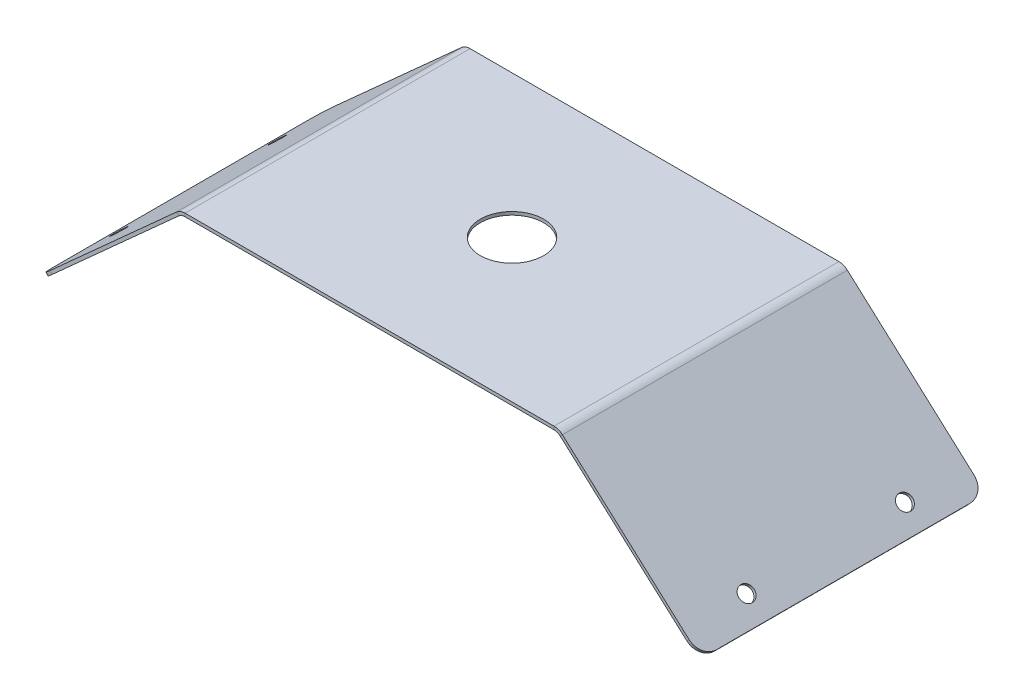
SolidWorks part; units mm, degrees
note: The reader was unsure of these and kept them because the rebuilt part matched: flange length of "Aresta-Flange1".
ref_plane "Plano frontal" through (0, 0, 0) normal (0, 0, 1) x (1, 0, 0)
ref_plane "Plano superior" through (0, 0, 0) normal (0, 1, 0) x (1, 0, 0)
ref_plane "Plano direito" through (0, 0, 0) normal (1, 0, 0) x (0, 0, -1)
sketch "Esboço1" plane through (0, 0, 0) normal (0, 1, 0) x (1, 0, 0)
  line L1 (-58.25, 45) -> (58.25, 45)
  line L2 (-58.25, 45) -> (-58.25, -45)
  line L3 (-58.25, -45) -> (58.25, -45)
  line L4 (58.25, 45) -> (58.25, -45)
  line L5 (-58.25, 45) -> (58.25, -45) construction
  line L6 (-58.25, -45) -> (58.25, 45) construction
  point P0 (0, 0)
  dimension "D1" = 116.5
  dimension "D2" = 90
base flange "Flange-base1" sketch "Esboço1" thickness 1 reverse thickness direction no parameters "D1"=3
edge flange "Aresta-Flange1" sketch "Esboço10" flange profiles "Esboço10", "Esboço11" flange angle 138 flange length 60 flange position bend outside bend radius 3 thickness 1 relief rectangular parameters "D6"=10, "D8"=1
sketch "Esboço10" plane through (58.25, -1, 0) normal (0.6691, 0.7431, 0) x (0, 0, 1)
  line L0 (45, 0) -> (-45, 0) construction
  line L1 (45, 0) -> (-45, 0)
  line L2 (-45, 0) -> (-45, 60)
  line L3 (-45, 60) -> (45, 60)
  line L4 (45, 60) -> (45, 0)
sketch "Esboço11" plane through (-58.25, -1, 0) normal (-0.6691, 0.7431, 0) x (0, 0, -1)
  line L0 (45, 0) -> (-45, 0) construction
  line L1 (45, 0) -> (-45, 0)
  line L2 (-45, 0) -> (-45, 60)
  line L3 (-45, 60) -> (45, 60)
  line L4 (45, 60) -> (45, 0)
bend "DobradeAresta1" bend radius 3 bend angle 42 parameters "D5"=1
bend "DobradeAresta2" bend radius 3 bend angle 42 parameters "D5"=2
sketch "Esboço12" plane through (26.7681, 29.729, 0) normal (0.6691, 0.7431, 0) x (0.7431, -0.6691, 0)
  line L0 (104.8131, -45) -> (104.8131, 45) construction
  line L1 (97.3131, -25) -> (97.3131, 25) construction
  line L2 (104.8131, 0) -> (97.3131, 0) construction
  line L3 (104.8131, 0) -> (45.9647, 0) construction
  line L4 (45.9647, -45) -> (45.9647, 45) construction
  line L5 (45.9647, 0) -> (75.3889, 45) construction
  line L6 (104.8131, 45) -> (45.9647, 45) construction
  line L7 (75.3889, 45) -> (75.3889, -45) construction
  line L8 (45.9647, -45) -> (104.8131, -45) construction
  circle A0 centre (97.3131, -25) radius 2.4
  circle A1 centre (97.3131, 25) radius 2.4
  circle A2 centre (79.8131, 0) radius 10 construction
  dimension "D2" = 4.8
  dimension "D4" = 20
  dimension "D1" = 50
  dimension "D3" = 7.5
  dimension "D5" = 25
extrude "Corte-extrusão1" cut sketch "Esboço12" against normal up to next normal cut yes
mirror "Espelhar1" about plane through (0, 0, 0) normal (1, 0, 0) of "Corte-extrusão1"
fillet "Filete1" radius 5 4 edges at (104.3248, -40.7763, 45) (104.3248, -40.7763, -45) (-104.3248, -40.7763, -45) (-104.3248, -40.7763, 45)
sketch "Esboço13" plane through (0, 0, 0) normal (0, 1, 0) x (1, 0, 0)
  line L0 (-58.25, 0) -> (58.25, 0) construction
  line L1 (-58.25, 45) -> (-58.25, -45) construction
  line L2 (58.25, -45) -> (58.25, 45) construction
  line L3 (0, 45) -> (0, -45) construction
  line L4 (58.25, 45) -> (-58.25, 45) construction
  line L5 (-58.25, -45) -> (58.25, -45) construction
  circle A0 centre (-43.25, 0) radius 10 construction
  circle A1 centre (43.25, 0) radius 10 construction
  circle A2 centre (0, 0) radius 10
  dimension "D1" = 20
  dimension "D2" = 15
  dimension "D3" = 15
extrude "Corte-extrusão2" cut sketch "Esboço13" against normal up to next normal cut yes
sketch "Curva-Linhas1" plane through (0, 0, 0) normal (0, 1, 0) x (1, 0, 0)
sketch "Caixa delimitadora1" plane through (0, 0, 0) normal (0, 1, 0) x (1, 0, 0)
sheet metal parameters "Chapa metálica(1)" thickness 1 parameters "D1"=3
flat pattern "Padrão-Plano(1)" [suppressed]
sketch "Curva-Linhas2" plane through (0, 0, 0) normal (0, 1, 0) x (1, 0, 0)
sketch "Caixa delimitadora2" [suppressed] plane through (0, 0, 0) normal (0, 1, 0) x (1, 0, 0)
sheet metal parameters "Chapa metálica(2)" thickness 1 parameters "D1"=3
flat pattern "Padrão-Plano(1)" [suppressed]
sketch "Curva-Linhas3" plane through (0, 0, 0) normal (0, 1, 0) x (1, 0, 0)
sketch "Caixa delimitadora3" [suppressed] plane through (0, 0, 0) normal (0, 1, 0) x (1, 0, 0)
bend of the flat pattern "Planificar-<DobradeAresta1>1"
bend of the flat pattern "Planificar-<DobradeAresta2>1"
sheet metal parameters "Chapa metálica(3)" thickness 1 parameters "D1"=3
flat pattern "Padrão-Plano(1)" [suppressed]
sketch "Curva-Linhas4" plane through (0, 0, 0) normal (0, 1, 0) x (1, 0, 0)
sketch "Caixa delimitadora4" [suppressed] plane through (0, 0, 0) normal (0, 1, 0) x (1, 0, 0)
bend of the flat pattern "Planificar-<DobradeAresta1>2"
bend of the flat pattern "Planificar-<DobradeAresta2>2"
sheet metal parameters "Chapa metálica(4)" thickness 1 parameters "D1"=3
flat pattern "Padrão-Plano(1)" [suppressed]
sketch "Curva-Linhas5" plane through (0, 0, 0) normal (0, 1, 0) x (1, 0, 0)
sketch "Caixa delimitadora5" [suppressed] plane through (0, 0, 0) normal (0, 1, 0) x (1, 0, 0)
bend of the flat pattern "Planificar-<DobradeAresta1>3"
bend of the flat pattern "Planificar-<DobradeAresta2>3"
sheet metal parameters "Chapa metálica(5)" thickness 1 parameters "D1"=3
flat pattern "Padrão-Plano(1)" [suppressed]
sketch "Curva-Linhas6" plane through (0, 0, 0) normal (0, 1, 0) x (1, 0, 0)
sketch "Caixa delimitadora6" [suppressed] plane through (0, 0, 0) normal (0, 1, 0) x (1, 0, 0)
bend of the flat pattern "Planificar-<DobradeAresta1>4"
bend of the flat pattern "Planificar-<DobradeAresta2>4"
